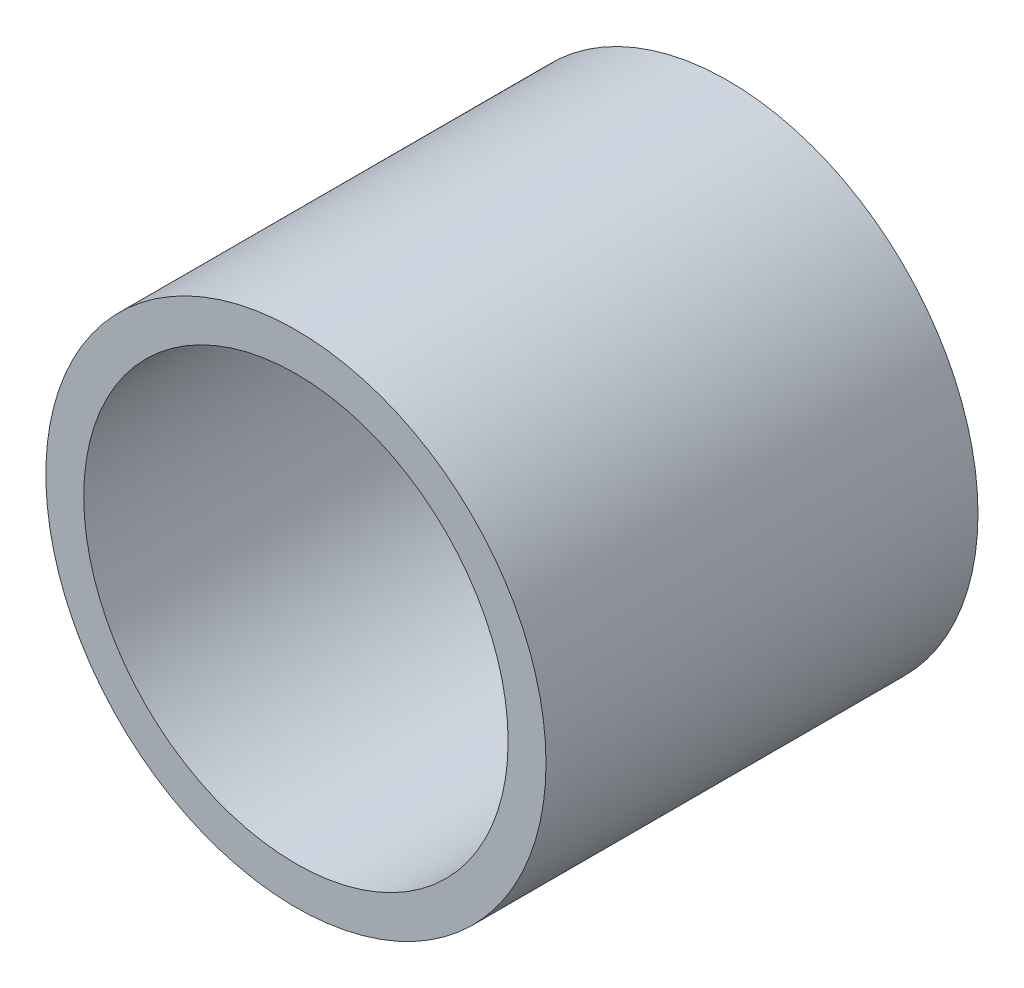
SolidWorks part; units mm, degrees
ref_plane "Front Plane" through (0, 0, 0) normal (0, 0, 1) x (1, 0, 0)
ref_plane "Top Plane" through (0, 0, 0) normal (0, 1, 0) x (1, 0, 0)
ref_plane "Right Plane" through (0, 0, 0) normal (1, 0, 0) x (0, 0, -1)
sketch "Sketch1" plane through (0, 0, 0) normal (0, 0, 1) x (1, 0, 0)
  circle A0 centre (0, 0) radius 2.8
  circle A1 centre (0, 0) radius 3.3
  dimension "D1" = 5.6
  dimension "D2" = 0.5
extrude "Boss-Extrude1" add sketch "Sketch1" along normal blind 5.7
